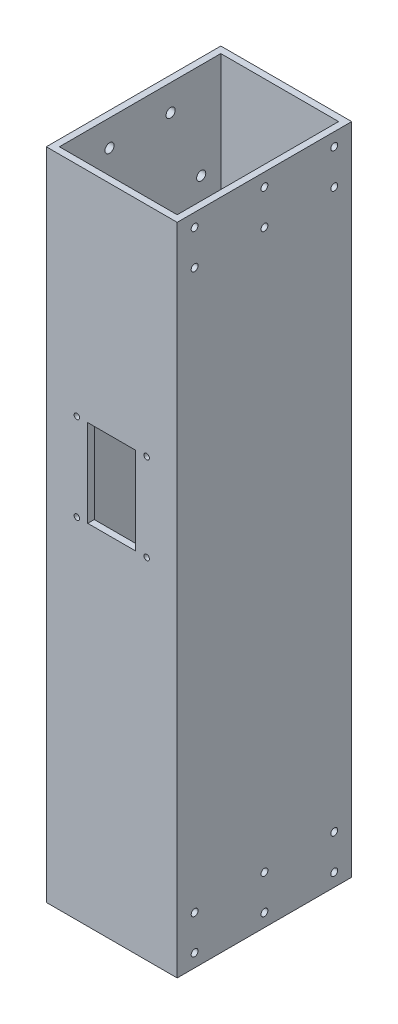
SolidWorks part; units mm, degrees
material "6061-T6 (SS)"
ref_plane "Front Plane" through (0, 0, 0) normal (0, 0, 1) x (1, 0, 0)
ref_plane "Top Plane" through (0, 0, 0) normal (0, 1, 0) x (1, 0, 0)
ref_plane "Right Plane" through (0, 0, 0) normal (1, 0, 0) x (0, 0, -1)
sketch "Sketch1" plane through (0, 0, 0) normal (0, 1, 0) x (1, 0, 0)
  line L0 (3, 3) -> (3, 77)
  line L1 (0, 0) -> (60, 0)
  line L2 (0, 0) -> (0, 80)
  line L3 (0, 80) -> (60, 80)
  line L4 (60, 0) -> (60, 80)
  line L5 (3, 77) -> (57, 77)
  line L6 (57, 3) -> (57, 77)
  line L7 (3, 3) -> (57, 3)
  dimension "D1" = 80
  dimension "D2" = 60
  dimension "D3" = 3
extrude "Boss-Extrude1" add sketch "Sketch1" along normal blind 300
sketch "Sketch2" plane through (0, 0, 0) normal (0, 0, 1) x (1, 0, 0)
  line L0 (30, 300) -> (30, 200) construction
  line L1 (19, 200) -> (41, 200)
  line L2 (19, 200) -> (19, 160)
  line L3 (19, 160) -> (41, 160)
  line L4 (41, 200) -> (41, 160)
  line L5 (0, 300) -> (60, 300) construction
  dimension "D1" = 22
  dimension "D2" = 100
  dimension "D3" = 40
extrude "Cut-Extrude1" cut sketch "Sketch2" against normal up to next
sketch "Sketch3" plane through (0, 0, 0) normal (0, 0, 1) x (1, 0, 0)
  line L0 (19, 200) -> (19, 160) construction
  line L2 (41, 160) -> (41, 200) construction
  line L3 (14, 200) -> (19, 200) construction
  point P0 (14, 200)
  point P11 (46, 200)
  point P12 (46, 160)
  point P13 (14, 160)
  dimension "D1" = 5
  dimension "D5" = 5
  dimension "D6" = 40
  dimension "D3" = 2
  dimension "D4" = 2
hole_wizard "Tap Drill for M3 Tap1" positions "Sketch3" profile "Sketch5" hole size "M3" standard "DIN" end condition up to next
sketch "Sketch5" plane through (14, 200, 0) normal (1, 0, 0) x (0, -1, 0)
  line L0 (0, 0) -> (0, 3)
  line L1 (0, 3) -> (1.25, 3)
  line L2 (1.25, 3) -> (1.25, 0)
  line L5 (1.25, 0) -> (0, 0)
  line L11 (0, -6.35) -> (0, 107.95) construction
  dimension "Thru Hole Dia." = 2.5
  dimension "Thru Hole Depth" = 3
sketch "Sketch8" plane through (0, 0, 0) normal (-1, 0, 0) x (0, 0, 1)
  point P0 (-8, 6)
  point P8 (-40, 6)
  point P9 (-72, 6)
  point P10 (-40, 22)
  point P11 (-72, 22)
  point P12 (-8, 22)
  dimension "D1" = 3
  dimension "D2" = 2
hole_wizard "Tap Drill for M3 Helicoil1" positions "Sketch8" profile "Sketch7" hole size "M3x0.5" standard "DIN" end condition through all
sketch "Sketch7" plane through (0, 6, -8) normal (0, 1, 0) x (0, 0, 1)
  line L0 (0, 0) -> (0, 60)
  line L1 (0, 60) -> (1.575, 60)
  line L2 (1.575, 60) -> (1.575, 0)
  line L5 (1.575, 0) -> (0, 0)
  line L11 (0, -6.35) -> (0, 107.95) construction
  dimension "Thru Hole Dia." = 3.15
  dimension "Thru Hole Depth" = 60
sketch "Sketch11" plane through (60, 0, 0) normal (1, 0, 0) x (0, 0, -1)
  line L3 (40, 300) -> (40, 248.3318) construction
  line L4 (0, 300) -> (80, 300) construction
  point P45 (8, 294)
  point P50 (40, 294)
  point P51 (72, 294)
  point P52 (40, 278)
  point P53 (72, 278)
  point P54 (8, 278)
  point P61 (0, 0)
  dimension "D1" = 3
  dimension "D3" = 6
  dimension "D2" = 2
hole_wizard "Tap Drill for M3 Helicoil2" positions "Sketch11" profile "Sketch10" hole size "M3x0.5" standard "DIN" end condition up to next
sketch "Sketch10" plane through (60, 294, -8) normal (0, 1, 0) x (0, 0, -1)
  line L0 (0, 0) -> (0, 3)
  line L1 (0, 3) -> (1.575, 3)
  line L2 (1.575, 3) -> (1.575, 0)
  line L5 (1.575, 0) -> (0, 0)
  line L11 (0, -6.35) -> (0, 107.95) construction
  dimension "Thru Hole Dia." = 3.15
  dimension "Thru Hole Depth" = 3
sketch "Sketch14" plane through (0, 0, 0) normal (-1, 0, 0) x (0, 0, 1)
  point P0 (-68, 256)
  point P3 (-12, 256)
  point P6 (-26, 288)
  point P9 (-54, 288)
hole_wizard "Tap Drill for M5 Tap1" positions "Sketch14" profile "Sketch13" hole size "M5" standard "DIN" end condition up to next
sketch "Sketch13" plane through (0, 256, -68) normal (0, 1, 0) x (0, 0, 1)
  line L0 (0, 0) -> (0, 3)
  line L1 (0, 3) -> (2.1, 3)
  line L2 (2.1, 3) -> (2.1, 0)
  line L5 (2.1, 0) -> (0, 0)
  line L11 (0, -6.35) -> (0, 107.95) construction
  dimension "Thru Hole Dia." = 4.2
  dimension "Thru Hole Depth" = 3
